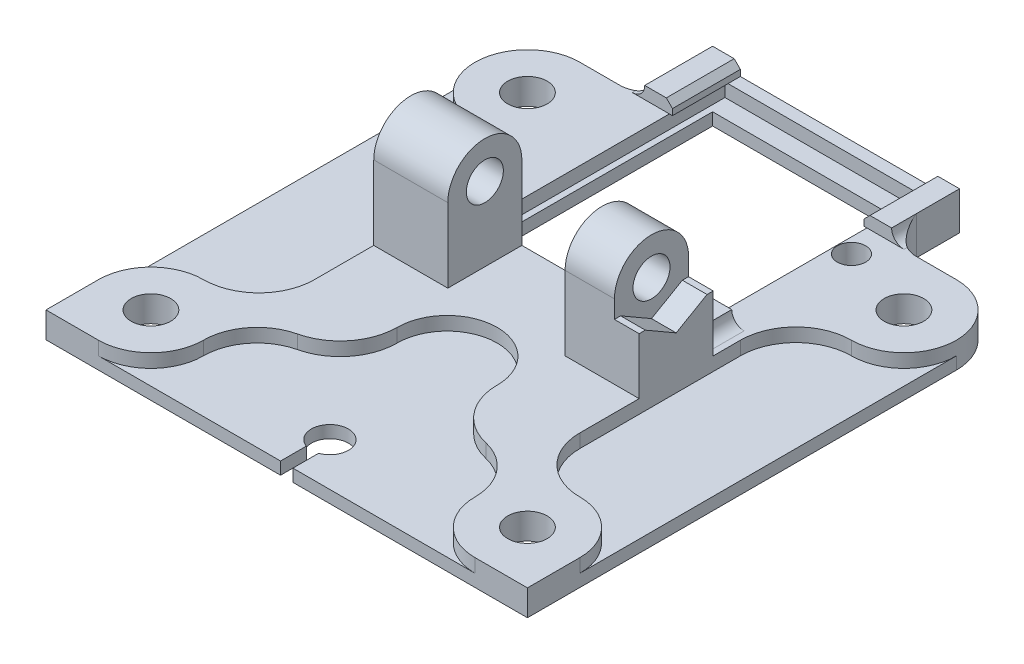
SolidWorks part; units mm, degrees
ref_plane "Front Plane" through (0, 0, 0) normal (0, 0, 1) x (1, 0, 0)
ref_plane "Top Plane" through (0, 0, 0) normal (0, 1, 0) x (1, 0, 0)
ref_plane "Right Plane" through (0, 0, 0) normal (1, 0, 0) x (0, 0, -1)
sketch "Sketch1" plane through (0, 0, 0) normal (0, 1, 0) x (1, 0, 0)
  line L0 (-19.5, 35.2) -> (-19.5, -19.5) construction
  line L1 (-19.5, 19.5) -> (19.5, 19.5)
  line L2 (-19.5, 19.5) -> (-19.5, -19.5)
  line L3 (-19.5, -19.5) -> (19.5, -19.5)
  line L4 (19.5, 19.5) -> (19.5, -19.5)
  line L5 (-19.5, 19.5) -> (19.5, -19.5) construction
  line L6 (-19.5, -19.5) -> (19.5, 19.5) construction
  line L7 (-19.5, -19.5) -> (19.5, -19.5) construction
  line L8 (0, -19.5) -> (0, 19.5) construction
  line L9 (-0.5, -19.5) -> (-0.5, -17.4142)
  line L10 (0.5, -19.5) -> (0.5, -17.4142)
  circle A0 centre (-15.25, -15.25) radius 1.6 construction
  circle A1 centre (15.25, -15.25) radius 1.6 construction
  circle A2 centre (9.2, 17.05) radius 1.15 construction
  circle A3 centre (15.25, 15.25) radius 1.6 construction
  circle A4 centre (-15.25, 15.25) radius 1.6 construction
  circle A5 centre (-15.25, -15.25) radius 1.6
  circle A6 centre (15.25, -15.25) radius 1.6
  circle A7 centre (9.2, 17.05) radius 1.15
  circle A8 centre (15.25, 15.25) radius 1.6
  circle A9 centre (-15.25, 15.25) radius 1.6
  circle A10 centre (-15.25, 15.25) radius 4.25
  circle A11 centre (15.25, 15.25) radius 4.25
  circle A12 centre (-15.25, -15.25) radius 4.25
  circle A13 centre (15.25, -15.25) radius 4.25
  circle A14 centre (0, -16) radius 1.5
  point P0 (0, 0)
  dimension "D1" = 3
  dimension "D2" = 3.5
  dimension "D3" = 1
extrude "Shape" add sketch "Sketch1" along normal blind 2.1 contours A13 L4 A11 L1 A10 L2 A12 L3 A7 | A10 A9 | A11 A8 | A13 A6 | A12 A5 | A12 L2 L3 | A13 L3 L4 region at (-0.0302, 0, -0.063) region at (-12.3298, 0, -18.1702) region at (18.1702, 0, -18.1702) region at (-18.5507, 0, 18.5507) region at (-15.25, 0, 11.1202) region at (18.1702, 0, 18.1702) region at (18.5507, 0, 18.5507)
sketch "Sketch3" plane through (0, 2.1, 0) normal (0, 1, 0) x (1, 0, 0)
  line L0 (0, 19.5) -> (0, -19.5) construction
  line L1 (-15.25, 19.5) -> (15.25, 19.5) construction
  line L3 (-19.5, 1.3) -> (19.5, 1.3) construction
  line L4 (-19.5, 15.25) -> (-19.5, -19.5) construction
  line L5 (19.5, 15.25) -> (19.5, -19.5) construction
  line L6 (4.75, 4.3) -> (10.75, 4.3)
  line L7 (-4.75, 4.3) -> (-10.75, 4.3)
  line L8 (-4.75, 4.3) -> (-4.75, -1.7)
  line L9 (-4.75, -1.7) -> (-10.75, -1.7)
  line L10 (-10.75, 4.3) -> (-10.75, -1.7)
  line L11 (-4.75, 4.3) -> (-10.75, -1.7) construction
  line L12 (-4.75, -1.7) -> (-10.75, 4.3) construction
  line L13 (4.75, 4.3) -> (4.75, -1.7)
  line L14 (4.75, -1.7) -> (10.75, -1.7)
  line L15 (10.75, 4.3) -> (10.75, -1.7)
  line L16 (-19.5, -19.5) -> (19.5, -19.5) construction
  line L18 (10.75, 4.3) -> (10.75, -1.7)
  point P12 (-7.75, 1.3)
  dimension "D1" = 18.2
  dimension "D2" = 9.5
  dimension "D3" = 6
  dimension "D4" = 6
extrude "Supports" add sketch "Sketch3" along normal blind 9 contours L7 L10 L9 L8 | L15 L6 L13 L14 region at (7.75, 2.1, -1.3) region at (-7.75, 2.1, -1.3)
sketch "Sketch4" plane through (-10.75, 0, 0) normal (-1, 0, 0) x (0, 0, 1)
  line L0 (-1.3, 11.1) -> (-1.3, 2.1) construction
  line L2 (-4.3, 2.1) -> (1.7, 2.1) construction
  line L3 (1.7, 11.1) -> (1.7, 2.1) construction
  line L4 (-4.3, 11.1) -> (1.7, 11.1) construction
  circle A0 centre (-1.3, 8.1) radius 3
  circle A1 centre (-1.3, 8.1) radius 1.5
  line M2 (1.7, 2.1) -> (1.7, 11.1)
  line M4 (-4.3, 11.1) -> (-4.3, 2.1)
  line M11 (1.7, 11.1) -> (-4.3, 11.1)
  dimension "D1" = 3
extrude "Support cuts" cut sketch "Sketch4" against normal up to surface (21.5 mm away) contours A1 L0 | L0 A1 | A0 M11 M4 | A0 M2 M11 region at (-10.75, 10.4299, 1.0299) region at (-10.75, 10.4299, -3.6299) region at (-10.75, 8.1, -0.6634) region at (-10.75, 8.1, -1.9366) up to face at (10.75, 6.6, -1.3)
sketch "Sketch5" plane through (10.75, 0, 0) normal (1, 0, 0) x (0, 0, -1)
  line L0 (-1.2, 6.6566) -> (-1.7, 6.6566)
  line L1 (1.3, 5.2132) -> (3.8, 6.6566)
  line L2 (3.8, 6.6566) -> (3.8, 9.5434)
  line L3 (3.8, 9.5434) -> (1.3, 10.9868)
  line L4 (1.3, 10.9868) -> (-1.2, 9.5434)
  line L5 (-1.2, 9.5434) -> (-1.2, 6.6566)
  line L6 (-1.2, 6.6566) -> (1.3, 5.2132)
  line L7 (3.8, 6.6566) -> (4.3, 6.6566)
  line L8 (4.3, 2.1) -> (-1.7, 2.1) construction
  line L9 (-1.7, 8.1) -> (-1.7, 2.1) construction
  line L10 (4.3, 8.1) -> (4.3, 2.1) construction
  line L12 (-1.7, 8.1) -> (-1.7, 2.1)
  line L13 (-1.7, 2.1) -> (4.3, 2.1)
  line L14 (4.3, 2.1) -> (4.3, 8.1)
  circle A0 centre (1.3, 8.1) radius 2.5 construction
  arc A2 (4.3, 8.1) -> (-1.7, 8.1) centre (1.3, 8.1) ccw construction
  arc A3 (4.3, 8.1) -> (-1.7, 8.1) centre (1.3, 8.1) ccw
  dimension "D1" = 5
extrude "Nut holder" cut sketch "Sketch5" against normal blind 2 contours L5 L6 L1 L2 L3 L4 | L2 L7 L0 L5 L4 L3 region at (10.75, 6.7313, 1.45) region at (10.75, 8.1, -1.3)
sketch "Sketch6" plane through (-10.75, 0, 0) normal (-1, 0, 0) x (0, 0, 1)
  circle A0 centre (-1.3, 8.1) radius 1.95
  dimension "D1" = 3.9
extrude "Screw cut" cut sketch "Sketch6" against normal offset from surface (3.5 mm away) 18 up to face at (10.75, 5.1485, -1.3)
sketch "Sketch9" plane through (0, 2.1, 0) normal (0, 1, 0) x (1, 0, 0)
  line L0 (8, 4.5) -> (8, 24) construction
  line L1 (8, 24) -> (-8, 24) construction
  line L2 (-8, 24) -> (-8, 4.5) construction
  line L3 (8, 4.5) -> (8, 24)
  line L4 (8, 24) -> (-8, 24)
  line L5 (-8, 24) -> (-8, 4.5)
  line L6 (-15.25, 19.5) -> (15.25, 19.5) construction
  line L7 (-15.25, 19.5) -> (15.25, 19.5)
  line L8 (-8, 24) -> (8, 19.5) construction
  line L9 (-8, 24) -> (8, 24)
  line L14 (10, 25) -> (-10, 25)
  line L15 (10, 25) -> (10, 18.5)
  line L16 (10, 18.5) -> (-10, 18.5)
  line L17 (-10, 25) -> (-10, 18.5)
  line L18 (10, 25) -> (-10, 18.5) construction
  line L19 (10, 18.5) -> (-10, 25) construction
  point P10 (0, 21.75)
  line M5 (15.25, 19.5) -> (-15.25, 19.5)
  dimension "D1" = 1
  dimension "D2" = 2
extrude "Datalogger front" add sketch "Sketch9" against normal up to surface (2.1 mm away) contours L4 L5 L3 M5 | L14 L17 L5 L4 L3 L7 L15 M5 region at (0, 2.1, -21.75) region at (8.2074, 2.1, -21.75) up to face at (0, 0, 3.8654)
sketch "Sketch10" plane through (0, 0, -25) normal (0, 0, -1) x (-1, 0, 0)
  line L1 (-8, 2.1) -> (8, 2.1)
  line L2 (-8, 2.1) -> (-8, 1)
  line L3 (-8, 1) -> (8, 1)
  line L4 (8, 2.1) -> (8, 1)
  line L6 (-8, 1) -> (8, 1) construction
  line L8 (8, 2.1) -> (8, 1) construction
extrude "Datalogger main cut" cut sketch "Sketch10" against normal offset from surface (20.7 mm away) 0.2 offset beyond the face yes
sketch "Sketch11" plane through (0, 1, 0) normal (0, 1, 0) x (1, 0, 0)
  line L6 (-7.5, 22.5) -> (7.5, 22.5)
  line L9 (8, 25) -> (-8, 25) construction
  line L12 (-7.5, 4.8) -> (7.5, 4.8)
  line L13 (7.5, 4.8) -> (7.5, 24.5)
  line L14 (7.5, 24.5) -> (-7.5, 24.5)
  line L15 (7.5, 24.5) -> (-7.5, 24.5)
  line L17 (-7.5, 24.5) -> (-7.5, 4.8)
  line L18 (-7.5, 4.8) -> (7.5, 4.8)
  line L19 (7.5, 4.8) -> (7.5, 24.5)
  line L23 (-7.5, 24.5) -> (-7.5, 4.8)
  dimension "D2" = 2.5
  dimension "D1" = 0.5
extrude "Datalogger bottom cut" cut sketch "Sketch11" against normal up to next contours L23 L18 L19 region at (0, 1, -13.65)
sketch "Sketch12" plane through (0, 1, 0) normal (0, 1, 0) x (1, 0, 0)
  line L1 (-8, 25) -> (8, 25)
  line L2 (-8, 25) -> (-8, 24)
  line L3 (-8, 24) -> (8, 24)
  line L4 (8, 25) -> (8, 24)
  dimension "D1" = 1
extrude "Datalogger front retainer" add sketch "Sketch12" along normal up to surface (1.1 mm away) up to face at (0, 2.1, -4.5902)
sketch "Sketch13" plane through (0, 2.1, 0) normal (0, 1, 0) x (1, 0, 0)
  line L1 (-8, 4.3) -> (-9.25, 4.3)
  line L2 (-8, 4.3) -> (-8, 7.3)
  line L3 (-8, 7.3) -> (-9.25, 7.3)
  line L4 (-9.25, 4.3) -> (-9.25, 7.3)
  line L5 (-8, 7.3) -> (-7.75, 7.3)
  line L6 (-8, 7.3) -> (-8, 4.3)
  line L7 (-8, 4.3) -> (-7.75, 4.3)
  line L8 (-7.75, 7.3) -> (-7.75, 4.3)
  line L9 (0, 7.608) -> (0, -4.6396) construction
  line L10 (9.25, 4.3) -> (9.25, 7.3)
  line L11 (8, 7.3) -> (9.25, 7.3)
  line L12 (8, 7.3) -> (7.75, 7.3)
  line L13 (7.75, 7.3) -> (7.75, 4.3)
  line L14 (8, 4.3) -> (7.75, 4.3)
  line L15 (8, 4.3) -> (9.25, 4.3)
  line M8 (8, 24) -> (8, 4.3)
  line M9 (8, 4.3) -> (10.75, 4.3)
  line M25 (-10.75, 4.3) -> (-8, 4.3)
  line M26 (-8, 4.3) -> (-8, 24)
  dimension "D1" = 1.5
  dimension "D2" = 3
  dimension "D3" = 0.25
extrude "Datalogger rear retainers" add sketch "Sketch13" along normal blind 1 contours L4 L3 M25 M26 | L8 L5 L7 M26 | L14 L12 L13 M8 | L11 L10 M8 M9 region at (-8.625, 2.1, -5.8) region at (-7.875, 2.1, -5.8) region at (8.625, 2.1, -5.8) region at (7.875, 2.1, -5.8)
sketch "Sketch14" plane through (0, 2.1, 0) normal (0, 1, 0) x (1, 0, 0)
  line L0 (-15.25, 19.5) -> (-10, 19.5) construction
  line L1 (-10, 25) -> (-7.75, 25)
  line L2 (-10, 25) -> (-10, 19.5)
  line L3 (-10, 19.5) -> (-7.75, 19.5)
  line L4 (-7.75, 25) -> (-7.75, 19.5)
  line L5 (-8, 4.3) -> (-8, 24) construction
  line L6 (-19.5, -19.5) -> (19.5, -19.5) construction
  line L8 (0, 25) -> (0, -19.5) construction
  line L9 (10, 25) -> (-10, 25) construction
  line L11 (10, 25) -> (10, 19.5)
  line L12 (10, 25) -> (7.75, 25)
  line L13 (7.75, 25) -> (7.75, 19.5)
  line L14 (10, 19.5) -> (7.75, 19.5)
  line M43 (10, 19.5) -> (10, 25)
  line M45 (10, 25) -> (-10, 25)
  line M46 (8, 24) -> (8, 7.3)
  line M68 (-8, 7.3) -> (-8, 24)
  line M71 (-10, 25) -> (-10, 19.5)
  line M161 (-8, 24) -> (8, 24)
  dimension "D1" = 0.25
extrude "Datalogger side retainers" add sketch "Sketch14" along normal up to surface (1 mm away) contours M45 M161 M46 M43 | M71 M68 M161 | L4 L3 M161 M68 | L14 L13 M46 M161 region at (-8.975, 2.1, -22.3) region at (-7.875, 2.1, -21.75) region at (8.975, 2.1, -22.3) region at (7.875, 2.1, -21.75) up to face at (-8.5, 3.1, -5.8)
sketch "Sketch15" plane through (0, 0, -25) normal (0, 0, -1) x (-1, 0, 0)
  line L0 (-7.75, 2.6) -> (-8.25, 3.1)
  line L2 (-7.75, 3.1) -> (-7.75, 2.1) construction
  line L3 (-8.25, 3.1) -> (-7.75, 3.1)
  line L4 (-7.75, 3.1) -> (-7.75, 2.6)
  line L5 (0, 0) -> (0, 2.1) construction
  line L6 (-7.75, 2.1) -> (7.75, 2.1) construction
  line L7 (8.25, 3.1) -> (7.75, 3.1)
  line L8 (7.75, 3.1) -> (7.75, 2.6)
  line L9 (7.75, 2.6) -> (8.25, 3.1)
  dimension "D1" = 45
extrude "Datalogger side retainer clips" cut sketch "Sketch15" against normal up to next
sketch "Sketch16" plane through (0, 2.1, 0) normal (0, 1, 0) x (1, 0, 0)
  line L0 (-19.5, 15.25) -> (-19.5, -19.5) construction
  line L1 (-15.25, 11) -> (-15.25, -11) construction
  line L2 (0, -2.4485) -> (-4.0515, -2.4485) construction
  line L3 (0, 25) -> (0, -19.5) construction
  line L4 (7.75, 25) -> (-7.75, 25) construction
  line L5 (-19.5, -19.5) -> (-0.5, -19.5) construction
  line L6 (-15.25, -11) -> (0, -11) construction
  line L7 (-11, -15.25) -> (0, -15.25) construction
  line L8 (-4.0515, 25) -> (-4.0515, -19.5) construction
  line L9 (-10.75, 4.3) -> (-10.75, -1.7) construction
  line L10 (-10.75, 6.5) -> (-10.75, 19.5) construction
  line L11 (-10, 19.5) -> (-8, 19.5) construction
  line L12 (-19.5, 15.25) -> (-19.5, -15.25)
  line L13 (-10.75, -1.7) -> (-10.75, -11) construction
  line L14 (-10.75, -6.5) -> (0, -6.5) construction
  line L15 (-15.25, 11) -> (-10.75, 11) construction
  line L16 (-10.75, 6.5) -> (-10.75, -6.5)
  line L17 (-4.75, -1.7) -> (-10.75, -1.7) construction
  line L18 (10.75, 6.5) -> (10.75, -6.5)
  line L19 (-15.25, -19.5) -> (15.25, -19.5)
  circle A0 centre (-15.25, 15.25) radius 4.25
  circle A1 centre (-15.25, -15.25) radius 4.25
  arc A2 (-15.25, 19.5) -> (-19.5, 15.25) centre (-15.25, 15.25) ccw construction
  arc A3 (-15.25, 11) -> (-10.75, 6.5) centre (-15.25, 6.5) cw
  arc A4 (-15.25, -11) -> (-10.75, -6.5) centre (-15.25, -6.5) ccw
  arc A5 (-11, -15.25) -> (-7.625, -11) centre (-6.6366, -15.25) cw
  arc A6 (-7.625, -11) -> (-4.0515, -6.5) centre (-8.6716, -6.5) ccw
  arc A7 (-4.0515, -6.5) -> (4.0515, -6.5) centre (0, -6.5) cw
  arc A8 (7.625, -11) -> (4.0515, -6.5) centre (8.6716, -6.5) cw
  arc A9 (11, -15.25) -> (7.625, -11) centre (6.6366, -15.25) ccw
  circle A10 centre (15.25, -15.25) radius 4.25
  arc A11 (15.25, -11) -> (10.75, -6.5) centre (15.25, -6.5) cw
  arc A12 (15.25, 11) -> (10.75, 6.5) centre (15.25, 6.5) ccw
  circle A13 centre (15.25, 15.25) radius 4.25
  line M39 (-19.5, 15.25) -> (-19.5, -19.5)
  line M40 (-19.5, -19.5) -> (-0.5, -19.5)
  line M41 (19.5, -19.5) -> (19.5, 15.25)
  arc M45 (-0.5, -17.4142) -> (0.5, -17.4142) centre (0, -16) cw
extrude "Weight cut" cut sketch "Sketch16" against normal offset from surface (1.1 mm away) 1 contours A1 A0 M39 | A10 A9 A8 A7 A6 A5 A1 M40 M45 | A13 L18 A10 M41 region at (-15.4165, 2.1, 0) region at (0, 2.1, 13.3087) region at (15.4165, 2.1, 0) up to face at (15.25, 0, 16.85)
fillet "Fillets" radius 2 2 edges at (10, 1.05, -19.5) (-10, 1.05, -19.5)
fillet "Fillet2" radius 1 4 edges at (10, 2.1, -20.5) (9.25, 2.1, -5.8) (-10, 2.1, -20.5) (-9.25, 2.1, -5.8)
